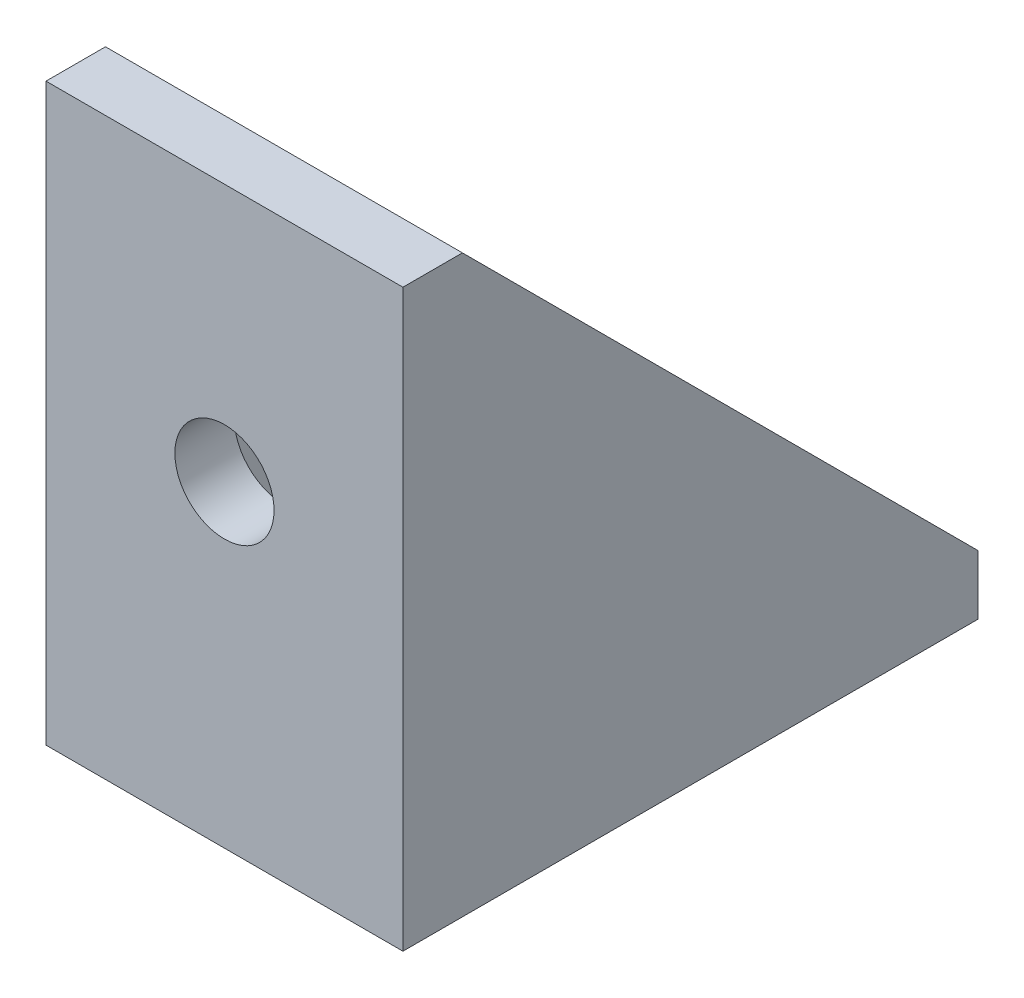
SolidWorks part; units mm, degrees
ref_plane "Front Plane" through (0, 0, 0) normal (0, 0, 1) x (1, 0, 0)
ref_plane "Top Plane" through (0, 0, 0) normal (0, 1, 0) x (1, 0, 0)
ref_plane "Right Plane" through (0, 0, 0) normal (1, 0, 0) x (0, 0, -1)
sketch "Sketch1" plane through (0, 0, 0) normal (1, 0, 0) x (0, 0, -1)
  line L0 (0, 29) -> (0, 0)
  line L1 (0, 0) -> (29, 0)
  dimension "D1" = 29
extrude "Extrude-Thin1" add sketch "Sketch1" along normal blind 9 and the other way blind 9 thin thin type one direction reverse wall 3
sketch "Sketch2" plane through (9, 0, 0) normal (1, 0, 0) x (0, 0, -1)
  line L0 (3, 29) -> (29, 3)
rib "Rib1" sketch "Sketch2" sketch "Sketch2" thickness 2 extrusion direction parallel to sketch draft on no parameters "D1"=2
mirror "Mirror1" about plane through (0, 0, 0) normal (1, 0, 0) of "Rib1"
sketch "Sketch3" plane through (0, 3, 0) normal (0, 1, 0) x (1, 0, 0)
  line L0 (0, 3) -> (0, 29) construction
  line L1 (-7, 3) -> (7, 3) construction
  line L2 (-7, 29) -> (7, 29) construction
  circle A0 centre (0, 16) radius 2.5
  dimension "D1" = 5
extrude "Cut-Extrude1" cut sketch "Sketch3" against normal blind 10
sketch "Sketch4" plane through (0, 0, -3) normal (0, 0, -1) x (-1, 0, 0)
  line L0 (0, 29) -> (0, 3) construction
  line L1 (7, 29) -> (-7, 29) construction
  line L2 (7, 3) -> (-7, 3) construction
  circle A0 centre (0, 16) radius 2.5
  dimension "D1" = 5
extrude "Cut-Extrude2" cut sketch "Sketch4" against normal blind 10
